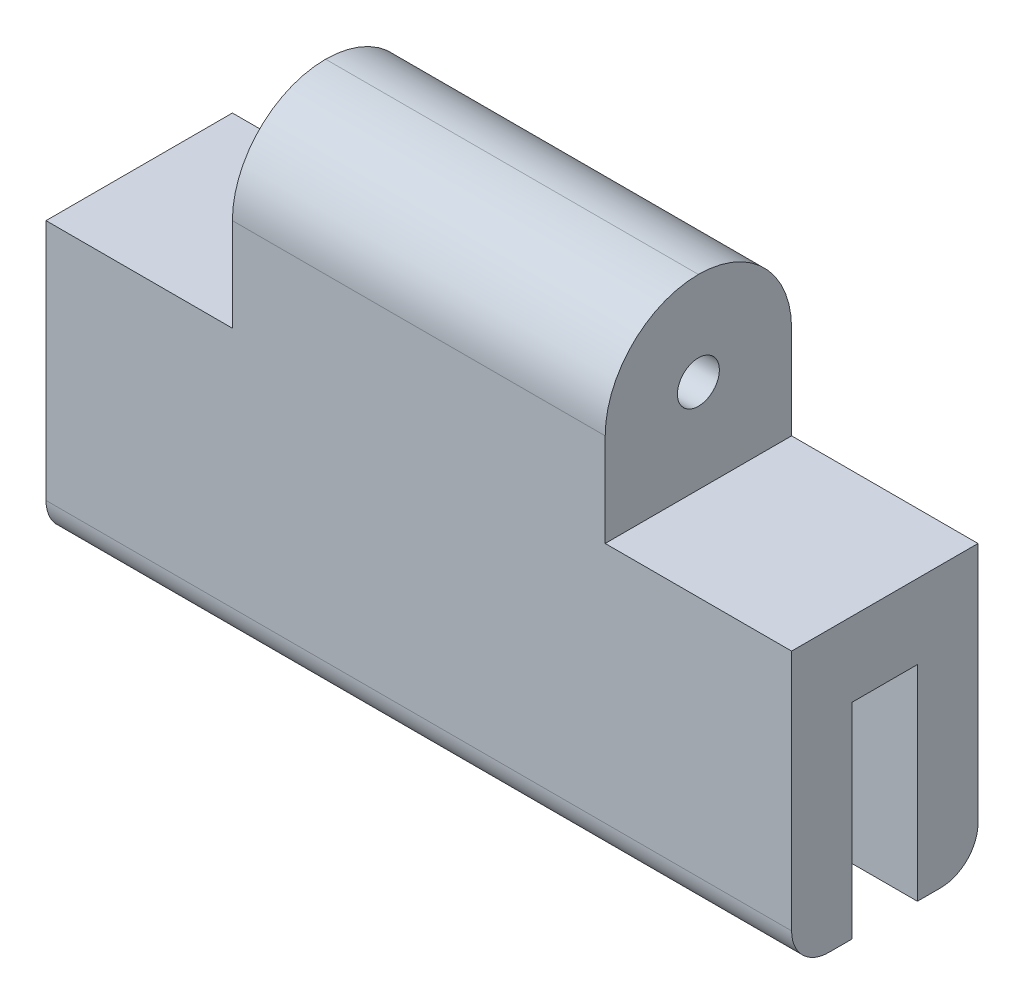
SolidWorks part; units mm, degrees
ref_plane "Front" through (0, 0, 0) normal (0, 0, 1) x (1, 0, 0)
ref_plane "Top" through (0, 0, 0) normal (0, 1, 0) x (1, 0, 0)
ref_plane "Right" through (0, 0, 0) normal (1, 0, 0) x (0, 0, -1)
sketch "Sketch1" plane through (0, 0, 0) normal (0, 1, 0) x (1, 0, 0)
  line L1 (0, 0) -> (80, 0)
  line L2 (0, 0) -> (0, -20)
  line L3 (0, -20) -> (80, -20)
  line L4 (80, 0) -> (80, -20)
  dimension "D1" = 20
  dimension "D2" = 80
extrude "Boss-Extrude1" add sketch "Sketch1" along normal blind 30
sketch "Sketch2" plane through (0, 0, 0) normal (0, -1, 0) x (-1, 0, 0)
  line L0 (0, 0) -> (0, -20) construction
  line L1 (0, -6.5) -> (-80, -6.5)
  line L2 (0, -6.5) -> (0, -13.5)
  line L3 (0, -13.5) -> (-80, -13.5)
  line L4 (-80, -6.5) -> (-80, -13.5)
  line L5 (-80, -20) -> (-80, 0) construction
  line L6 (-80, 0) -> (0, 0) construction
  dimension "D1" = 7
  dimension "D2" = 6.5
extrude "Cut-Extrude1" cut sketch "Sketch2" against normal blind 22
sketch "Sketch3" plane through (0, 30, 0) normal (0, 1, 0) x (1, 0, 0)
  line L0 (80, 0) -> (0, 0) construction
  line L1 (20, 0) -> (60, 0)
  line L2 (20, 0) -> (20, -20)
  line L3 (20, -20) -> (60, -20)
  line L4 (60, 0) -> (60, -20)
  line L5 (0, -20) -> (80, -20) construction
  line L6 (0, 0) -> (0, -20) construction
  dimension "D1" = 40
  dimension "D2" = 20
extrude "Boss-Extrude2" add sketch "Sketch3" along normal blind 20
sketch "Sketch4" plane through (20, 0, 0) normal (-1, 0, 0) x (0, 0, 1)
  line L0 (20, 50) -> (20, 30) construction
  line L1 (0, 50) -> (20, 50) construction
  circle A0 centre (10, 40) radius 2.25
  dimension "D1" = 4.5
  dimension "D2" = 10
  dimension "D3" = 10
extrude "Cut-Extrude2" cut sketch "Sketch4" against normal through all
fillet "Fillet1" radius 10 2 edges at (40, 50, 0) (40, 50, 20)
fillet "Fillet2" radius 4 2 edges at (40, 0, 0) (40, 0, 20)
